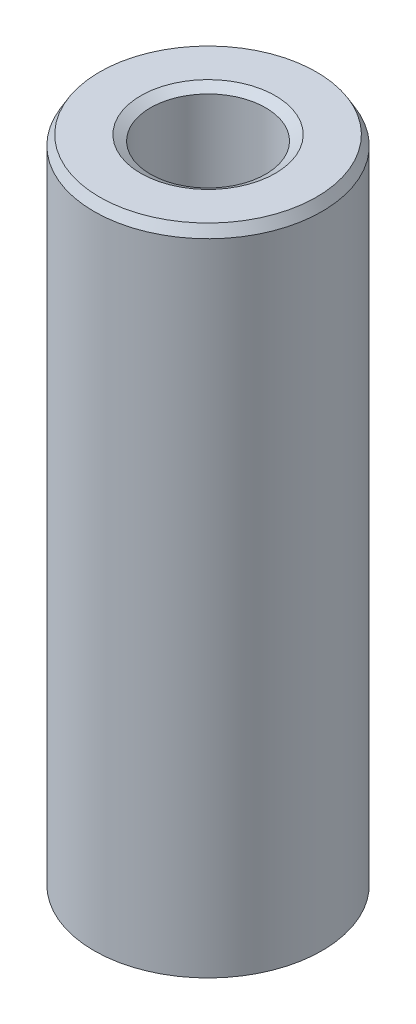
SolidWorks part; units mm, degrees
ref_plane "Front Plane" through (0, 0, 0) normal (0, 0, 1) x (1, 0, 0)
ref_plane "Top Plane" through (0, 0, 0) normal (0, 1, 0) x (1, 0, 0)
ref_plane "Right Plane" through (0, 0, 0) normal (1, 0, 0) x (0, 0, -1)
sketch "Sketch1" plane through (0, 0, 0) normal (0, 1, 0) x (1, 0, 0)
  circle A0 centre (0, 0) radius 10
  dimension "SLEEVE_OD" = 20
extrude "Boss-Extrude1" add sketch "Sketch1" along normal blind 57.4883
sketch "Sketch2" plane through (0, 0, 0) normal (0, 1, 0) x (1, 0, 0)
  circle A0 centre (0, 0) radius 5.0544
  dimension "BORE_D" = 10.1088
extrude "Cut-Extrude1" cut sketch "Sketch2" along normal through all
chamfer "Chamfer1" distance 0.8478 angle 30 4 edges at (0, 57.4883, 5.0544) (0, 0, 5.0544) (0, 0, 10) (0, 57.4883, 10) first distance on face at (0, 57.4883, 5.0544) first distance on face at (0, 0, 5.0544) first distance on face at (0, 57.4883, 10)
